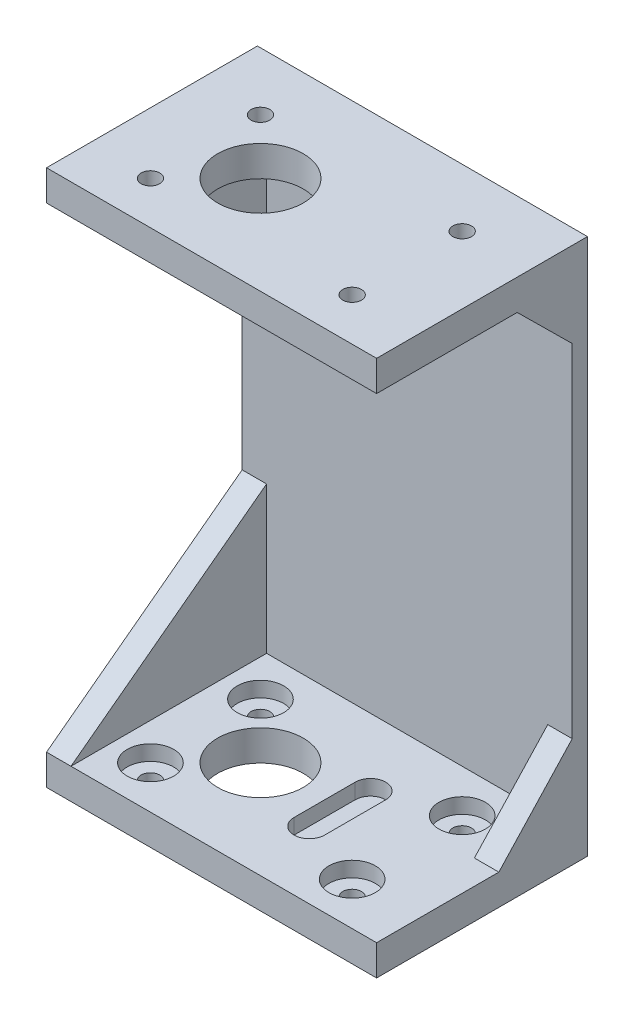
SolidWorks part; units mm, degrees
ref_plane "Front" through (0, 0, 0) normal (0, 0, 1) x (1, 0, 0)
ref_plane "Top" through (0, 0, 0) normal (0, 1, 0) x (1, 0, 0)
ref_plane "Right" through (0, 0, 0) normal (1, 0, 0) x (0, 0, -1)
sketch "Sketch2" plane through (0, 0, 0) normal (0, 1, 0) x (1, 0, 0)
  line L1 (-23, -16) -> (23, -16)
  line L2 (-23, -16) -> (-23, 16)
  line L3 (-23, 16) -> (23, 16)
  line L4 (23, -16) -> (23, 16)
  line L5 (-23, -16) -> (23, 16) construction
  line L6 (-23, 16) -> (23, -16) construction
  circle A0 centre (-17, 9) radius 1.525
  circle A1 centre (-17, -9) radius 1.525
  circle A2 centre (16, -9) radius 1.525
  circle A3 centre (16, 9) radius 1.525
  circle A4 centre (-8, 0) radius 7
  point P0 (0, 0)
  dimension "D3" = 3.05
  dimension "D4" = 7
  dimension "D5" = 6
  dimension "D6" = 7
  dimension "D7" = 7
  dimension "D8" = 7
  dimension "D9" = 7
  dimension "D10" = 7
  dimension "D11" = 6
  dimension "D12" = 14
  dimension "D13" = 15
  dimension "D14" = 16
  dimension "D1" = 46
  dimension "D2" = 32
extrude "Boss-Extrude1" add sketch "Sketch2" along normal blind 5
sketch "Sketch3" plane through (0, 5, 0) normal (0, 1, 0) x (1, 0, 0)
  line L0 (5, 5) -> (5, -5) construction
  line L1 (7.5, 5) -> (7.5, -5)
  line L2 (2.5, 5) -> (2.5, -5)
  line L3 (-23, -16) -> (23, -16) construction
  line L4 (-23, 16) -> (-23, -16) construction
  circle A0 centre (-17, 9) radius 3.8
  circle A1 centre (-17, -9) radius 3.8
  circle A2 centre (16, -9) radius 3.8
  circle A3 centre (16, 9) radius 3.8
  arc A4 (7.5, 5) -> (2.5, 5) centre (5, 5) ccw
  arc A5 (2.5, -5) -> (7.5, -5) centre (5, -5) ccw
  point P14 (5, 0)
  dimension "D1" = 7.6
  dimension "D3" = 2.5
  dimension "D2" = 10
  dimension "D4" = 11
  dimension "D5" = 28
extrude "Cut-Extrude1" cut sketch "Sketch3" against normal blind 2.5
sketch "Sketch4" plane through (0, 0, 0) normal (0, -1, 0) x (-1, 0, 0)
  line L3 (23, 16) -> (-23, 16)
  line L5 (27, 18.5) -> (-27, 18.5)
  line L6 (27, 18.5) -> (27, -16)
  line L7 (27, -16) -> (23, -16)
  line L8 (23, 16) -> (23, -16) construction
  line L9 (23, -16) -> (23, 16)
  line L10 (-27, 18.5) -> (-27, -16)
  line L11 (-27, -16) -> (-23, -16)
  line L13 (-23, -16) -> (-23, 16)
  dimension "D5" = 34.5
  dimension "D6" = 90
extrude "Boss-Extrude2" add sketch "Sketch4" against normal blind 87.8
extrude "Boss-Extrude3" add sketch "Sketch2<2>" against normal blind 5 from surface starting at face at (0, 87.8, -0.625)
sketch "Sketch2<2>" plane through (0, 0, 0) normal (0, 1, 0) x (1, 0, 0) same geometry as "Sketch2"
extrude "Cut-Extrude2" cut sketch "Sketch3<3>" along normal blind 2.5 from surface starting at face at (0, 82.8, 0)
sketch "Sketch3<3>" plane through (0, 5, 0) normal (0, 1, 0) x (1, 0, 0) same geometry as "Sketch3"
sketch "Sketch5" plane through (27, 0, 0) normal (1, 0, 0) x (0, 0, -1)
  line L0 (-16, 0) -> (-16, 5)
  line L1 (-16, 87.8) -> (-16, 0) construction
  line L2 (-16, 5) -> (4, 5)
  line L3 (4, 5) -> (16, 17.9)
  line L4 (16, 17.9) -> (16, 73.9)
  line L5 (16, 73.9) -> (7, 82.8)
  line L6 (7, 82.8) -> (-16, 82.8)
  line L7 (-16, 82.8) -> (-16, 5)
  line L8 (18.5, 87.8) -> (-16, 87.8) construction
  line L9 (18.5, 87.8) -> (18.5, 0) construction
  line L10 (-16, 43.9) -> (18.5, 43.9) construction
  line M8 (-16, 87.8) -> (-16, 0)
  dimension "D1" = 5
  dimension "D2" = 5
  dimension "D3" = 2.5
  dimension "D4" = 26
  dimension "D5" = 30
  dimension "D6" = 20
  dimension "D7" = 23
extrude "Cut-Extrude3" cut sketch "Sketch5" against normal blind 5 contours L10 L7 L2 L3 L4 | L10 L4 L5 L6 M8 region at (27, 25.4545, 0.7956) region at (27, 62.802, 0.4322)
sketch "Sketch6" plane through (-27, 0, 0) normal (-1, 0, 0) x (0, 0, 1)
  line L1 (16, 87.8) -> (16, 0) construction
  line L2 (16, 82.8) -> (16, 5)
  line L3 (-16, 58.8) -> (-16, 29)
  line L5 (16, 82.8) -> (-16, 58.8)
  line L6 (16, 5) -> (-16, 29)
  line L7 (-18.5, 87.8) -> (-18.5, 0) construction
  line L10 (16, 0) -> (-18.5, 0) construction
  line L11 (16, 87.8) -> (-18.5, 87.8) construction
  dimension "D3" = 2.5
  dimension "D4" = 29
  dimension "D5" = 29
extrude "Cut-Extrude4" cut sketch "Sketch6" against normal blind 5
